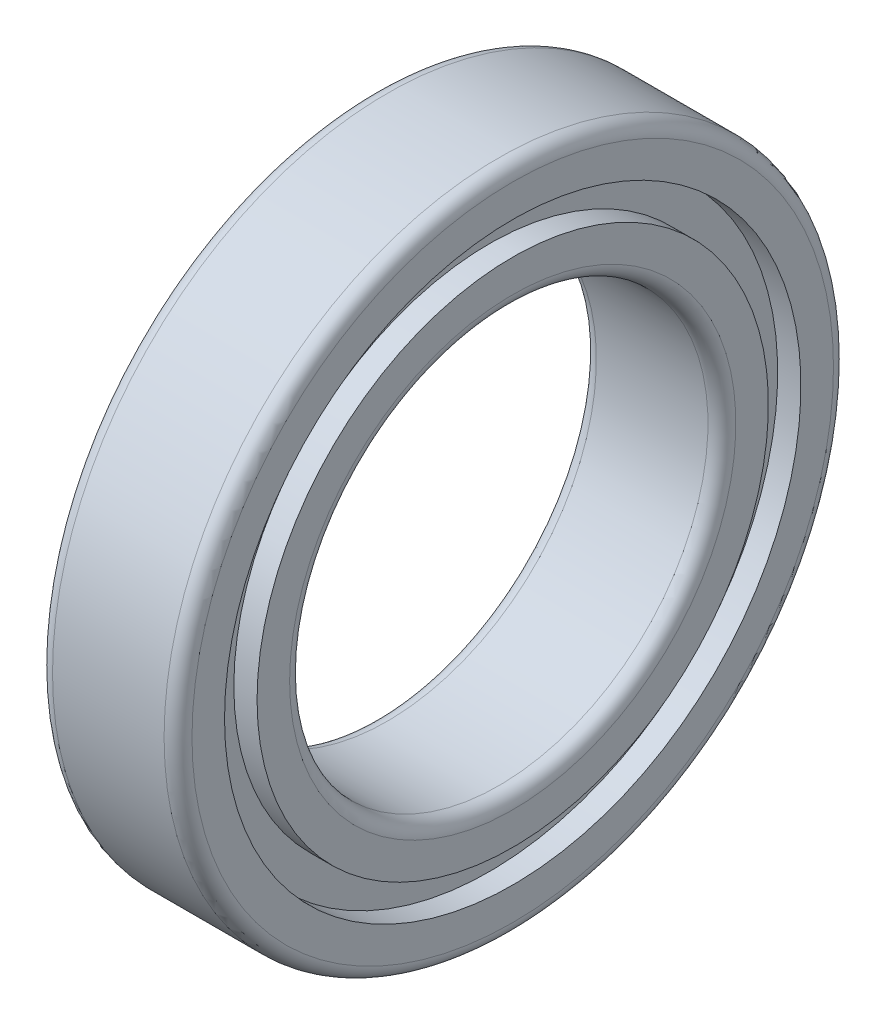
SolidWorks part; units mm, degrees
material "AISI 1020"
ref_plane "Спереди" through (0, 0, 0) normal (0, 0, 1) x (1, 0, 0)
ref_plane "Сверху" through (0, 0, 0) normal (0, 1, 0) x (1, 0, 0)
ref_plane "Справа" through (0, 0, 0) normal (1, 0, 0) x (0, 0, -1)
sketch "Эскиз1" plane through (0, 0, 0) normal (0, 0, 1) x (1, 0, 0)
  line L0 (-1000, 0) -> (49000, 0) construction
  line L1 (0, -1000) -> (0, 49000) construction
  line L2 (2, 7.5) -> (-2, 7.5)
  line L3 (-2.5, 8) -> (-2.5, 9.1667)
  line L4 (-2.5, 9.1667) -> (-1.6667, 9.1667)
  line L5 (-1.6667, 9.1667) -> (-1.6667, 10.3333)
  line L6 (-1.6667, 10.3333) -> (-2.5, 10.3333)
  line L7 (-2.5, 10.3333) -> (-2.5, 11.5)
  line L8 (-2, 12) -> (2, 12)
  line L9 (2.5, 10.3333) -> (2.5, 11.5)
  line L10 (1.6667, 10.3333) -> (2.5, 10.3333)
  line L11 (1.6667, 9.1667) -> (1.6667, 10.3333)
  line L12 (2.5, 9.1667) -> (1.6667, 9.1667)
  line L13 (2.5, 8) -> (2.5, 9.1667)
  arc A0 (-2, 7.5) -> (-2.5, 8) centre (-2, 8) cw
  arc A1 (-2.5, 11.5) -> (-2, 12) centre (-2, 11.5) cw
  arc A2 (2.5, 11.5) -> (2, 12) centre (2, 11.5) ccw
  arc A3 (2, 7.5) -> (2.5, 8) centre (2, 8) ccw
  point P23 (0, 12)
  point P27 (0, 7.5)
  dimension "_r" = 0.5
  dimension "_d" = 15
  dimension "D" = 24
  dimension "B" = 5
  dimension "D2" = 3.3333
revolve "Повернуть1" add sketch "Эскиз1" angle 360 about L0
other "PropertyManager" [suppressed]
equation "\"D2@Эскиз1\"= \"B@Эскиз1\" / 3 * 2"
